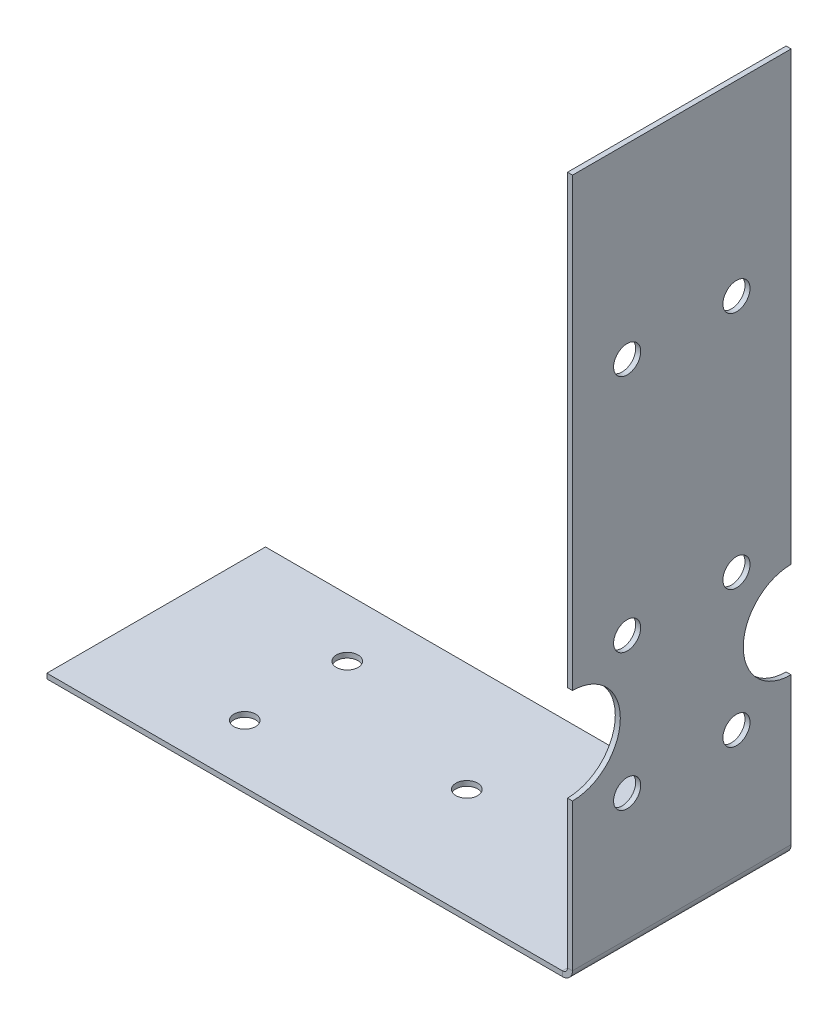
SolidWorks part; units mm, degrees
note: The reader was unsure of these and kept them because the rebuilt part matched: bend radius of "BaseBend1".
material "Plain Carbon Steel"
ref_plane "Front Plane" through (0, 0, 0) normal (0, 0, 1) x (1, 0, 0)
ref_plane "Top Plane" through (0, 0, 0) normal (0, 1, 0) x (1, 0, 0)
ref_plane "Right Plane" through (0, 0, 0) normal (1, 0, 0) x (0, 0, -1)
sketch "Sketch1" plane through (0, 0, 0) normal (0, 0, 1) x (1, 0, 0)
  line L0 (-76.2, 0) -> (0, 0)
  line L1 (0, 0) -> (0, 101.6)
  dimension "D1" = 76.2
  dimension "D2" = 101.6
base flange "Base-Flange1" sketch "Sketch1" end condition mid plane depth 32 reverse direction no thickness 0.7366 reverse thickness direction no bend radius 0.7366
bend "BaseBend1" bend radius 0.7366 bend angle 90 parameters "D5"=1
sketch "Sketch6" plane through (0, 0, 0) normal (-1, 0, 0) x (0, 0, 1)
  line L0 (16, -0.7366) -> (-16, -0.7366) construction
  line L2 (16, 0.7366) -> (16, 101.6) construction
  line L3 (0, -4.5823) -> (0, 122.7748) construction
  circle A0 centre (16, 29.2634) radius 7
  circle A1 centre (8, 19.2634) radius 1.9844
  circle A2 centre (8, 39.2634) radius 1.9844
  circle A3 centre (8, 74.2634) radius 1.9844
  circle A4 centre (-8, 19.2634) radius 1.9844
  circle A5 centre (-16, 29.2634) radius 7
  circle A6 centre (-8, 39.2634) radius 1.9844
  circle A7 centre (-8, 74.2634) radius 1.9844
  dimension "D1" = 14
  dimension "D3" = 3.9688
  dimension "D2" = 30
  dimension "D4" = 8
  dimension "D5" = 35
  dimension "D6" = 20
  dimension "D7" = 20
extrude "Cut-Extrude1" cut sketch "Sketch6" against normal blind 10 normal cut yes
sketch "Sketch7" plane through (0, 0, 0) normal (0, 1, 0) x (1, 0, 0)
  line L1 (-0.7366, -16) -> (-0.7366, 16) construction
  line L2 (-55.7366, 7.5) -> (-55.7366, -7.5) construction
  circle A0 centre (-30.7366, 0) radius 1.5875
  circle A1 centre (-55.7366, -7.5) radius 1.5875
  circle A2 centre (-55.7366, 7.5) radius 1.5875
  point P6 (-55.7366, 0)
  dimension "D1" = 3.175
  dimension "D2" = 25
  dimension "D3" = 30
  dimension "D4" = 15
extrude "Cut-Extrude2" cut sketch "Sketch7" against normal blind 10 normal cut yes
sketch "Bend-Lines1" [suppressed] plane through (0, 0, 0) normal (0, 1, 0) x (1, 0, 0)
sketch "Bounding-Box1" [suppressed] plane through (0, 0, 0) normal (0, 1, 0) x (1, 0, 0)
sheet metal parameters "Sheet-Metal3" thickness 0.7366 parameters "D1"=0.7366
flat pattern "Flat-Pattern3" [suppressed]
sketch "Bend-Lines2" plane through (0, 0, 0) normal (0, 1, 0) x (1, 0, 0)
sketch "Bounding-Box2" [suppressed] plane through (0, 0, 0) normal (0, 1, 0) x (1, 0, 0)
bend of the flat pattern "Flatten-<BaseBend1>1"
sheet metal parameters "Sheet-Metal4" thickness 0.7366 parameters "D1"=0.7366
flat pattern "Flat-Pattern3" [suppressed]
sketch "Bend-Lines2" plane through (0, 0, 0) normal (0, 1, 0) x (1, 0, 0)
sketch "Bounding-Box2" [suppressed] plane through (0, 0, 0) normal (0, 1, 0) x (1, 0, 0)
bend of the flat pattern "Flatten-<BaseBend1>1"
sheet metal parameters "Sheet-Metal5" thickness 0.7366 parameters "D1"=0.7366
flat pattern "Flat-Pattern3"
sketch "Bend-Lines2" plane through (0, 0, 0) normal (-1, 0, 0) x (0, 0, 1)
  line L0 (16, -0.1312) -> (-16, -0.1312) construction
  line L1 (16, -0.1312) -> (-16, -0.1312) construction
sketch3d "Bounding-Box2" [suppressed]
  line L0 (0, 101.6, 0) -> (0, -76.4624, 0) construction
  line L1 (-32, 101.6, 0) -> (-32, -76.4624, 0) construction
  line L2 (0, 101.6, 0) -> (-32, 101.6, 0) construction
  line L3 (0, -76.4624, 0) -> (-32, -76.4624, 0) construction
bend of the flat pattern "Flatten-<BaseBend1>1"
